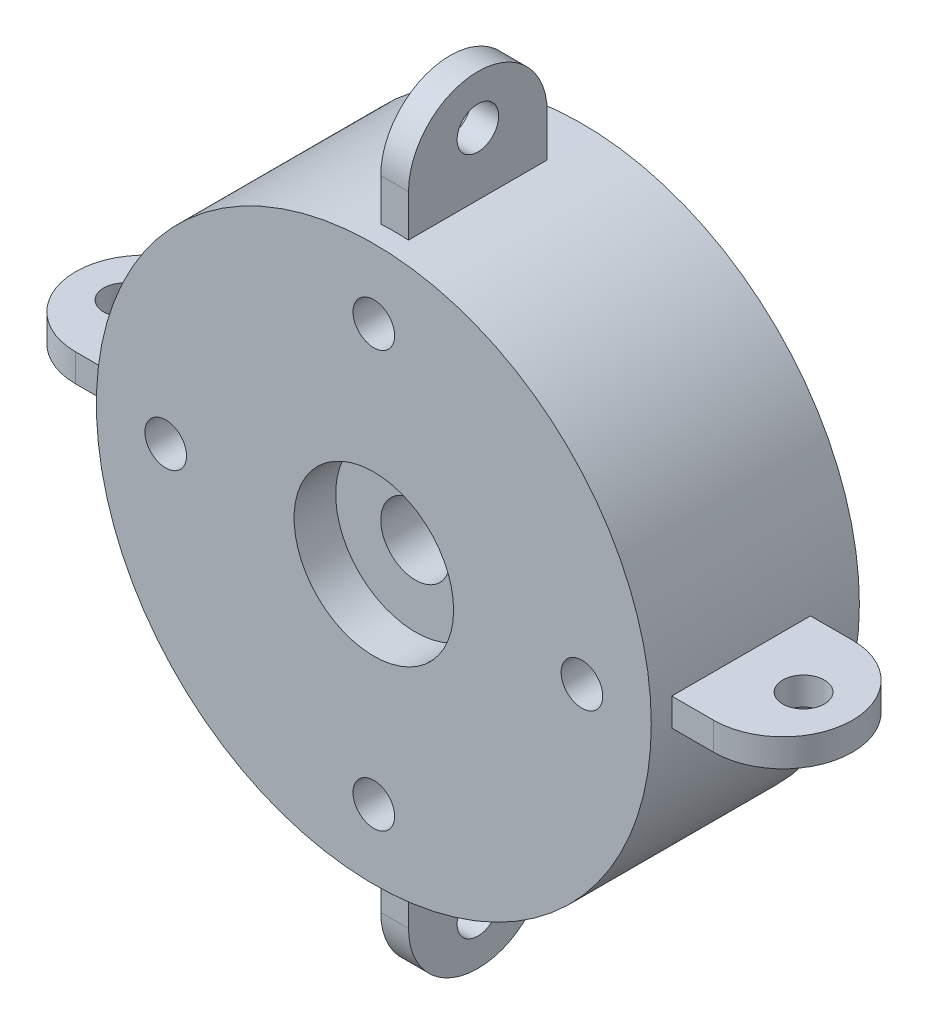
SolidWorks part; units mm, degrees
material "ABS"
ref_plane "前视基准面" through (0, 0, 0) normal (0, 0, 1) x (1, 0, 0)
ref_plane "上视基准面" through (0, 0, 0) normal (0, 1, 0) x (1, 0, 0)
ref_plane "右视基准面" through (0, 0, 0) normal (1, 0, 0) x (0, 0, -1)
sketch "草图1" plane through (0, 0, 0) normal (0, 0, 1) x (1, 0, 0)
  circle A0 centre (0, 0) radius 40
  dimension "D1" = 80
extrude "凸台-拉伸1" add sketch "草图1" along normal blind 30
sketch "草图2" plane through (0, 0, 30) normal (0, 0, 1) x (1, 0, 0)
  line L0 (0, 30) -> (0, 0) construction
  line L1 (0, 0) -> (0, -30) construction
  line L2 (-30, 0) -> (0, 0) construction
  line L3 (0, 0) -> (30, 0) construction
  circle A0 centre (30, 0) radius 3
  circle A1 centre (0, 30) radius 3
  circle A2 centre (-30, 0) radius 3
  circle A3 centre (0, -30) radius 3
  dimension "D1" = 6
  dimension "D2" = 6
  dimension "D7" = 6
  dimension "D8" = 6
  dimension "D3" = 30
  dimension "D4" = 30
  dimension "D5" = 30
  dimension "D6" = 30
extrude "切除-拉伸1" cut sketch "草图2" against normal through all
sketch "草图3" plane through (0, 0, 0) normal (1, 0, 0) x (0, 0, -1)
  line L0 (-7, 38) -> (-27, 38)
  line L1 (-27, 38) -> (-27, 46)
  line L2 (-7, 46) -> (-7, 38)
  line L3 (0, 0) -> (-35.6052, 0) construction
  arc A0 (-27, 46) -> (-7, 46) centre (-17, 46) cw
  dimension "D3" = 10
  dimension "D1" = 38
  dimension "D2" = 8
  dimension "D4" = 7
extrude "凸台-拉伸2" add sketch "草图3" along normal blind 2 and the other way blind 2
sketch "草图4" plane through (2, 0, 0) normal (1, 0, 0) x (0, 0, -1)
  line L0 (-27, 39.95) -> (-7, 39.95) construction
  line L1 (-7, 39.95) -> (-7, 46) construction
  circle A0 centre (-17, 48.95) radius 3
  dimension "D1" = 6
  dimension "D2" = 9
  dimension "D3" = 10
extrude "切除-拉伸2" cut sketch "草图4" against normal through all
pattern_circular "阵列(圆周)2" count 4 every 90 about axis through (0, 0, 30) along (0, 0, -1) of "凸台-拉伸2", "切除-拉伸2" reverse direction yes
sketch "草图5" plane through (0, 0, 0) normal (0, 0, -1) x (-1, 0, 0)
  circle A0 centre (0, 0) radius 5
  dimension "D1" = 10
extrude "切除-拉伸3" cut sketch "草图5" against normal up to next
sketch "草图6" plane through (0, 0, 30) normal (0, 0, 1) x (1, 0, 0)
  circle A0 centre (0, 0) radius 11.5
  dimension "D1" = 23
extrude "切除-拉伸4" cut sketch "草图6" against normal blind 6
